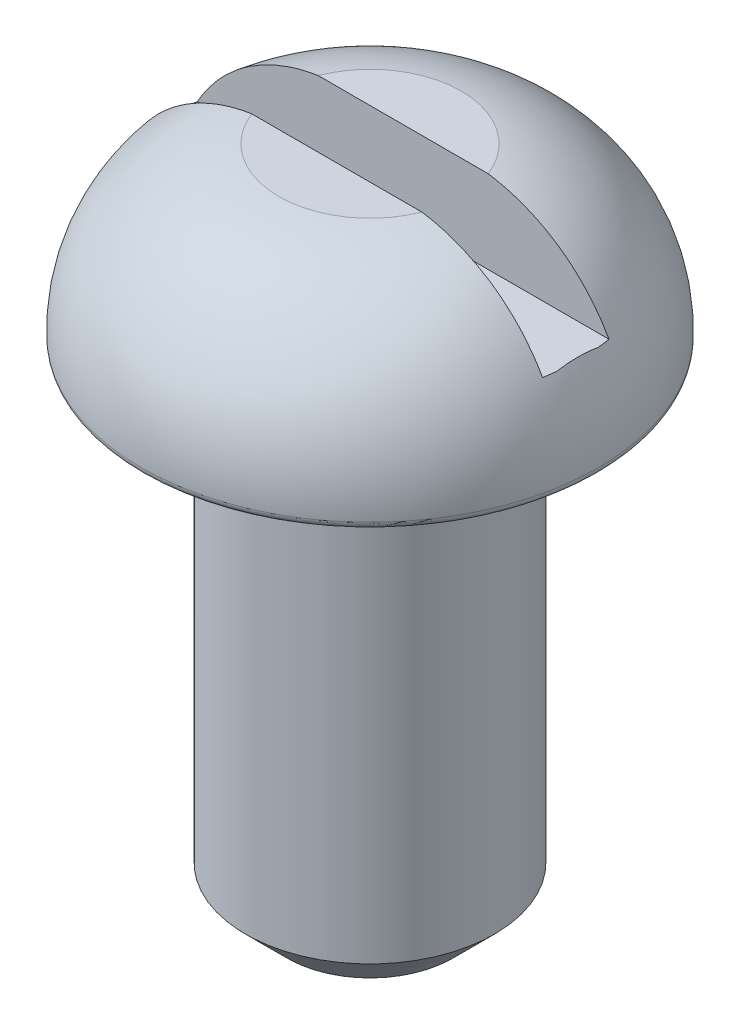
SolidWorks part; units mm, degrees
ref_plane "Спереди" through (0, 0, 0) normal (0, 0, 1) x (1, 0, 0)
ref_plane "Сверху" through (0, 0, 0) normal (0, 1, 0) x (1, 0, 0)
ref_plane "Справа" through (0, 0, 0) normal (1, 0, 0) x (0, 0, -1)
sketch "Эскиз1" plane through (0, 0, 0) normal (0, 0, 1) x (1, 0, 0)
  line L0 (2.75, 5.9) -> (1.5, 5.9)
  line L1 (0, 0) -> (0, 8)
  line L2 (1.5, 5.9) -> (1.5, 0.5)
  line L3 (1.5, 0.5) -> (1, 0)
  line L4 (1, 0) -> (0, 0)
  line L5 (0, 8) -> (1.1, 8)
  arc A0 (1.1, 8) -> (2.75, 5.9) centre (0.7797, 6.0501) cw
  dimension "D2" = 1.1
  dimension "D8" = 2.1
  dimension "D1" = 8
  dimension "D3" = 1.5
  dimension "D4" = 1
  dimension "D5" = 2.1
  dimension "D6" = 2.75
  dimension "D7" = 45
  dimension "D9" = 1.5
revolve "Повернуть1" add sketch "Эскиз1" angle 360 about L1
fillet "Скругление1" radius 0.1 1 edges at (0, 5.9, -2.75)
sketch "Эскиз3" plane through (0, 8, 0) normal (0, 1, 0) x (-1, 0, 0)
  line L1 (2.5, -0.4) -> (-2.5, -0.4)
  line L2 (2.5, -0.4) -> (2.5, 0.4)
  line L3 (2.5, 0.4) -> (-2.5, 0.4)
  line L4 (-2.5, -0.4) -> (-2.5, 0.4)
  dimension "D1" = 0.8
  dimension "D2" = 0.4
  dimension "D3" = 5
  dimension "D4" = 2.5
extrude "Вырез-Вытянуть2" cut sketch "Эскиз3" against normal blind 1
ref_axis "Ось1" through (0, -104.1565, 0) along (0, 1, 0)
